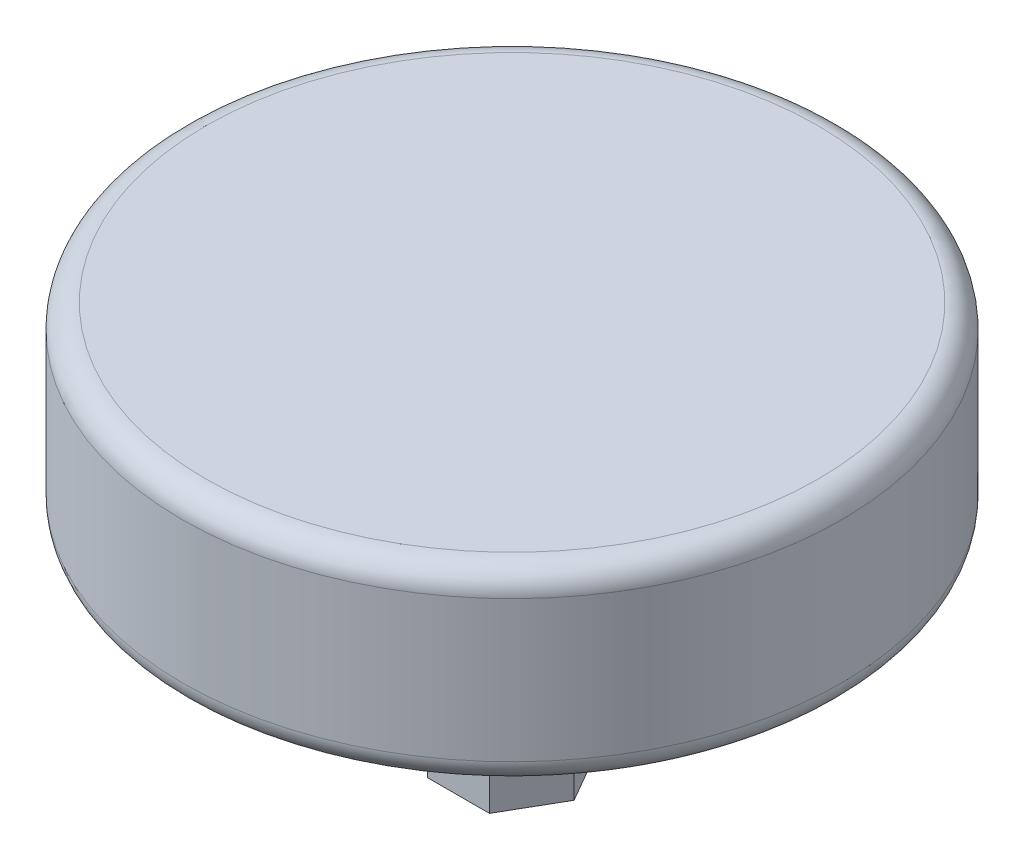
SolidWorks part; units mm, degrees
ref_plane "Front Plane" through (0, 0, 0) normal (0, 0, 1) x (1, 0, 0)
ref_plane "Top Plane" through (0, 0, 0) normal (0, 1, 0) x (1, 0, 0)
ref_plane "Right Plane" through (0, 0, 0) normal (1, 0, 0) x (0, 0, -1)
sketch "Sketch1" plane through (0, 0, 0) normal (0, 1, 0) x (1, 0, 0)
  line L1 (0.6582, 0) -> (0.3291, 0.57)
  line L2 (0.3291, 0.57) -> (-0.3291, 0.57)
  line L3 (-0.3291, 0.57) -> (-0.6582, 0)
  line L4 (-0.6582, 0) -> (-0.3291, -0.57)
  line L5 (-0.3291, -0.57) -> (0.3291, -0.57)
  line L6 (0.3291, -0.57) -> (0.6582, 0)
  circle A0 centre (0, 0) radius 0.57 construction
extrude "Boss-Extrude1" add sketch "Sketch1" along normal blind 1.75
sketch "Sketch2" plane through (0, 1.75, 0) normal (0, 1, 0) x (1, 0, 0)
  line L0 (0, 0) -> (0, -0.1986)
  line L1 (0.6582, 0) -> (0.3291, 0.57)
  line L2 (0.3291, 0.57) -> (-0.3291, 0.57)
  line L3 (-0.3291, 0.57) -> (-0.6582, 0)
  line L4 (-0.6582, 0) -> (-0.3291, -0.57)
  line L5 (-0.3291, -0.57) -> (0.3291, -0.57)
  line L6 (0.3291, -0.57) -> (0.6582, 0)
  line L7 (4.375, 0) -> (-2.1875, 3.7889) construction
  line L8 (-2.1875, 3.7889) -> (-2.1875, -3.7889) construction
  line L9 (-2.1875, -3.7889) -> (4.375, 0) construction
  line L10 (0, -0.1986) -> (0, 0.1978)
  line L11 (0, 0.1978) -> (4.375, 0)
  line L12 (4.375, 0) -> (0, -0.1986)
  circle A0 centre (0, 0) radius 0.57 construction
  circle A1 centre (0, 0) radius 4.375 construction
  line M2 (0.6582, 0) -> (0.3291, 0.57)
extrude "Boss-Extrude2" add sketch "Sketch2" along normal blind 0.5 contours L12 L11 L6 M2 | L12 L6 L11 L10 L0 M2 region at (0.2973, 1.75, 0.0004) region at (1.8638, 1.75, 0.0003)
sketch "Sketch3" plane through (0, 1.75, 0) normal (0, 1, 0) x (1, 0, 0)
  line L0 (0.6582, 0) -> (0.3291, 0.57)
  line L1 (-0.6582, 0) -> (-0.3291, -0.57)
  line L2 (-0.3291, -0.57) -> (0.3291, -0.57)
  line L3 (0.3291, -0.57) -> (0.6582, 0)
  line L4 (0.3291, 0.57) -> (-0.3291, 0.57)
  line L5 (-0.3291, 0.57) -> (-0.6582, 0)
  circle A0 centre (0, 0) radius 0.6582 construction
extrude "Boss-Extrude5" add sketch "Sketch3" along normal blind 3.5
sketch "Sketch4" plane through (0, 5.25, 0) normal (0, 1, 0) x (1, 0, 0)
  circle A0 centre (0, 0) radius 3.5
extrude "Boss-Extrude7" add sketch "Sketch4" along normal blind 2
sketch "Sketch11" plane through (0, 1.75, 0) normal (0, -1, 0) x (-1, 0, 0)
  circle A0 centre (0, 0) radius 4.5054
  circle A1 centre (0, 0) radius 3.5
extrude "Cut-Extrude3" cut sketch "Sketch11" against normal blind 2
sketch "Sketch12" plane through (0, 0, 0) normal (0, -1, 0) x (-1, 0, 0)
  circle A0 centre (0, 0) radius 3.5
extrude "Cut-Extrude4" cut sketch "Sketch12" against normal blind 3
fillet "Fillet2" radius 1 6 edges at (-0.4936, 5.25, -0.285) (0, 5.25, -0.57) (0.4936, 5.25, -0.285) (0.4936, 5.25, 0.285) (-0.4936, 5.25, 0.285) (0, 5.25, 0.57)
fillet "Fillet3" radius 0.25 2 edges at (0, 7.25, 3.5) (0, 5.25, 3.5)
